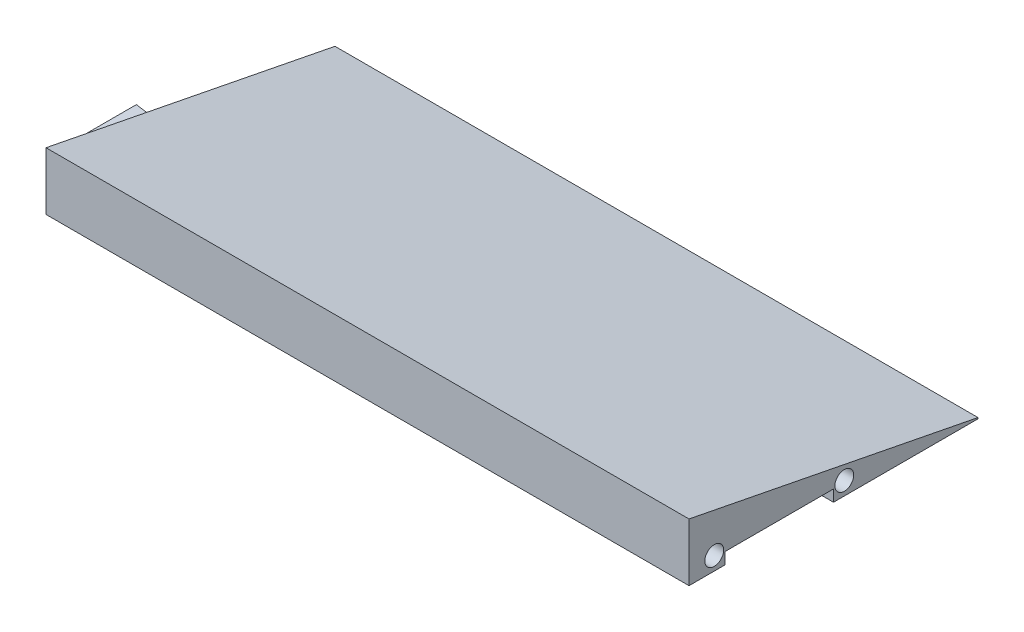
SolidWorks part; units mm, degrees
ref_plane "Front Plane" through (0, 0, 0) normal (0, 0, 1) x (1, 0, 0)
ref_plane "Top Plane" through (0, 0, 0) normal (0, 1, 0) x (1, 0, 0)
ref_plane "Right Plane" through (0, 0, 0) normal (1, 0, 0) x (0, 0, -1)
sketch "Sketch1" plane through (0, 0, 0) normal (1, 0, 0) x (0, 0, -1)
  line L0 (0, 0) -> (0, 20.32)
  line L1 (0, 20.32) -> (101.6, 0.4)
  line L2 (101.6, 0.4) -> (101.6, 0)
  line L3 (101.6, 0) -> (0, 0)
  dimension "D1" = 0.4
  dimension "D2" = 101.6
  dimension "D3" = 20.32
extrude "Boss-Extrude1" add sketch "Sketch1" along normal mid plane 391.16
sketch "Sketch2" plane through (195.58, 0, 0) normal (1, 0, 0) x (0, 0, -1)
  line L0 (0, 0) -> (101.6, 0) construction
  line L1 (101.6, 0.4) -> (0, 20.32) construction
  circle A0 centre (8.8764, 4.7625) radius 3.3147
  circle A1 centre (54.5964, 4.7625) radius 3.3147
  circle A2 centre (54.5964, 4.7625) radius 4.7625 construction
  circle A3 centre (8.8764, 4.7625) radius 4.7625 construction
  dimension "D1" = 45.72
  dimension "D2" = 6.6294
  dimension "D3" = 9.525
extrude "Cut-Extrude1" cut sketch "Sketch2" against normal blind 38.1
mirror "Mirror3" about plane through (0, 0, 0) normal (1, 0, 0) of "Cut-Extrude1"
sketch "Sketch3" plane through (-195.58, 0, 0) normal (-1, 0, 0) x (0, 0, 1)
  line L5 (0, 0) -> (-101.6, 0) construction
  line L6 (-50.8, 4.064) -> (-12.7, 4.064)
  line L7 (-50.8, 4.064) -> (-50.8, 0)
  line L8 (-50.8, 0) -> (-12.7, 0)
  line L9 (-12.7, 4.064) -> (-12.7, 0)
  line L10 (0, 20.32) -> (0, 0) construction
  dimension "D1" = 38.1
  dimension "D2" = 4.064
  dimension "D3" = 0
  dimension "D4" = 12.7
extrude "Cut-Extrude2" cut sketch "Sketch3" against normal through all
sketch "Sketch4" plane through (0, 0, 0) normal (0, -1, 0) x (1, 0, 0)
  line L1 (56.9178, -50.8) -> (56.9178, -60.2323) construction
  line L5 (73.1134, -60.2323) -> (73.1134, -50.8) construction
  line L7 (-10.2809, -12.7) -> (-10.2809, -3.2677) construction
  line L11 (124.1166, -50.8) -> (124.1166, -60.2323) construction
  line L18 (-10.2809, -50.8) -> (-11.6065, -60.2323)
  line L19 (-10.2809, -60.2323) -> (-11.6065, -60.2323)
  line L20 (-10.2809, -60.2323) -> (5.9146, -60.2323)
  line L21 (5.9146, -60.2323) -> (7.2403, -60.2323)
  line L22 (5.9146, -50.8) -> (7.2403, -60.2323)
  line L23 (-10.2809, -50.8) -> (5.9146, -50.8)
  line L24 (56.9178, -50.8) -> (55.5922, -60.2323)
  line L25 (56.9178, -60.2323) -> (55.5922, -60.2323)
  line L26 (56.9178, -60.2323) -> (73.1134, -60.2323)
  line L27 (73.1134, -60.2323) -> (74.439, -60.2323)
  line L28 (73.1134, -50.8) -> (74.439, -60.2323)
  line L29 (56.9178, -50.8) -> (73.1134, -50.8)
  line L30 (124.1166, -50.8) -> (122.791, -60.2323)
  line L31 (124.1166, -60.2323) -> (122.791, -60.2323)
  line L32 (124.1166, -60.2323) -> (140.3121, -60.2323)
  line L33 (140.3121, -60.2323) -> (141.6378, -60.2323)
  line L34 (140.3121, -50.8) -> (141.6378, -60.2323)
  line L35 (124.1166, -50.8) -> (140.3121, -50.8)
  line L42 (-195.58, -31.75) -> (195.58, -31.75) construction
  line L43 (-195.58, -12.7) -> (-195.58, -50.8) construction
  line L44 (195.58, -12.7) -> (195.58, -50.8) construction
  line L45 (-10.2809, -50.8) -> (-10.2809, -60.2323) construction
  line L52 (124.1166, -12.7) -> (140.3121, -12.7)
  line L53 (140.3121, -12.7) -> (141.6378, -3.2677)
  line L54 (140.3121, -3.2677) -> (141.6378, -3.2677)
  line L55 (124.1166, -3.2677) -> (140.3121, -3.2677)
  line L56 (124.1166, -3.2677) -> (122.791, -3.2677)
  line L57 (124.1166, -12.7) -> (122.791, -3.2677)
  line L58 (56.9178, -12.7) -> (73.1134, -12.7)
  line L59 (73.1134, -12.7) -> (74.439, -3.2677)
  line L60 (73.1134, -3.2677) -> (74.439, -3.2677)
  line L61 (56.9178, -3.2677) -> (73.1134, -3.2677)
  line L62 (56.9178, -3.2677) -> (55.5922, -3.2677)
  line L63 (56.9178, -12.7) -> (55.5922, -3.2677)
  line L64 (-10.2809, -12.7) -> (5.9146, -12.7)
  line L65 (5.9146, -12.7) -> (7.2403, -3.2677)
  line L66 (5.9146, -3.2677) -> (7.2403, -3.2677)
  line L67 (-10.2809, -3.2677) -> (5.9146, -3.2677)
  line L68 (-10.2809, -3.2677) -> (-11.6065, -3.2677)
  line L69 (-10.2809, -12.7) -> (-11.6065, -3.2677)
  line L82 (140.3121, -50.8) -> (140.3121, -60.2323) construction
  line L83 (195.58, 0) -> (195.58, -12.7) construction
  line L84 (5.9146, -3.2677) -> (5.9146, -12.7) construction
  line L88 (5.9146, -50.8) -> (5.9146, -60.2323) construction
  dimension "D2" = 55.2679
  dimension "D3" = 51.0032
  dimension "D4" = 51.0032
  dimension "D5" = 8
  dimension "D7" = 9.525
  dimension "D8" = 18.8468
  dimension "D9" = 8
  dimension "D10" = 8
  dimension "D6" = 8
  dimension "D11" = 9.525
  dimension "D12" = 18.8468
  dimension "D13" = 16.1956
  dimension "D14" = 8
  dimension "D15" = 8
  dimension "D16" = 18.8468
  dimension "D17" = 9.525
  dimension "D18" = 16.1956
  dimension "D19" = 8
  dimension "D20" = 8
  dimension "D21" = 9.525
  dimension "D22" = 9.525
  dimension "D23" = 18.8468
extrude "Cut-Extrude3" cut sketch "Sketch4" against normal blind 4.064
sketch "Sketch5" plane through (-195.58, 0, 0) normal (-1, 0, 0) x (0, 0, 1)
  line L1 (-101.6, 0) -> (0, 0)
  line L2 (-101.6, 0) -> (-101.6, 20.32)
  line L3 (-101.6, 20.32) -> (0, 20.32)
  line L4 (0, 0) -> (0, 20.32)
extrude "Cut-Extrude4" cut sketch "Sketch5" against normal blind 165.1
sketch "Sketch6" plane through (0, 4.064, 0) normal (0, -1, 0) x (1, 0, 0)
  line L0 (-30.48, -23.495) -> (-30.48, -39.8938)
  line L1 (-30.48, -12.7) -> (-30.48, -50.8) construction
  line L2 (-30.48, -39.8938) -> (-39.9123, -41.2194)
  line L3 (-39.9123, -41.2194) -> (-39.9123, -22.1694)
  line L4 (-39.9123, -22.1694) -> (-30.48, -23.495)
  line L5 (-30.48, -23.495) -> (-39.9123, -23.495) construction
  line L6 (-30.48, -39.8938) -> (-39.9123, -39.8938) construction
  line L7 (-10.2809, -12.7) -> (-30.48, -12.7) construction
  dimension "D1" = 8
  dimension "D2" = 8
  dimension "D3" = 19.05
  dimension "D4" = 9.525
  dimension "D5" = 10.795
extrude "Boss-Extrude2" add sketch "Sketch6" against normal blind 4.064
sketch "Sketch7" plane through (-30.48, 0, 0) normal (-1, 0, 0) x (0, 0, 1)
  line L0 (0, 0) -> (0, 20.32) construction
  line L1 (-12.7, 4.064) -> (-23.495, 4.064) construction
  line L2 (-39.8938, 4.064) -> (-50.8, 4.064) construction
  circle A0 centre (-15.24, 8.128) radius 1.905
  circle A1 centre (-45.72, 8.128) radius 1.905
  dimension "D4" = 3.81
  dimension "D5" = 3.81
  dimension "D1" = 15.24
  dimension "D2" = 30.48
  dimension "D3" = 4.064
  dimension "D6" = 4.064
extrude "Cut-Extrude5" cut sketch "Sketch7" against normal blind 12.7
